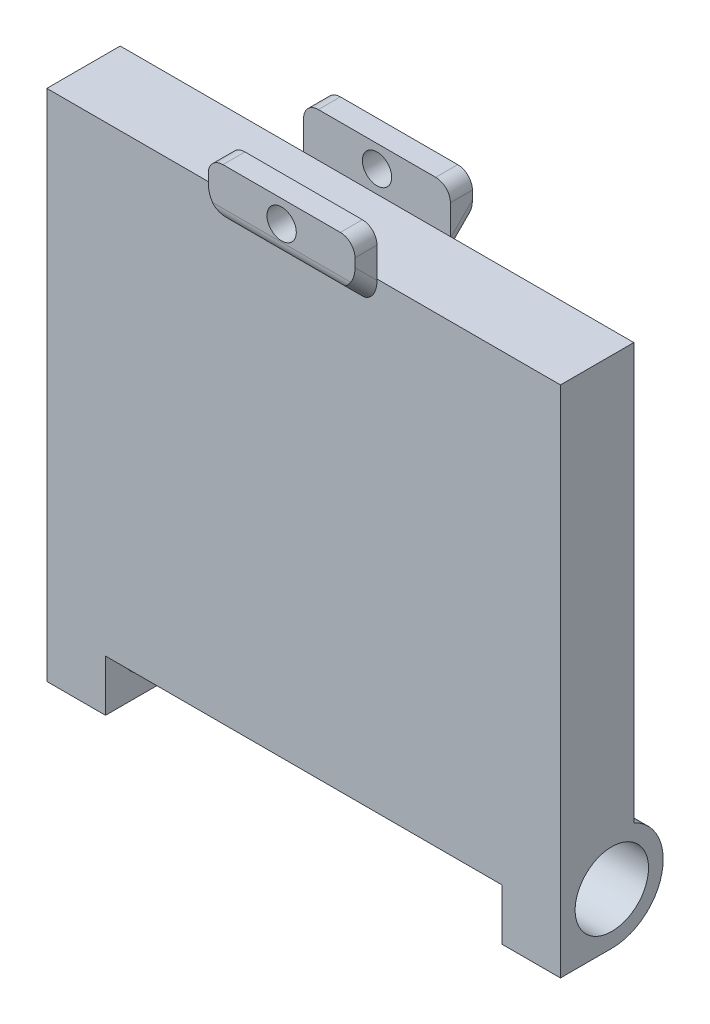
SolidWorks part; units mm, degrees
ref_plane "Front Plane" through (0, 0, 0) normal (0, 0, 1) x (1, 0, 0)
ref_plane "Top Plane" through (0, 0, 0) normal (0, 1, 0) x (1, 0, 0)
ref_plane "Right Plane" through (0, 0, 0) normal (1, 0, 0) x (0, 0, -1)
sketch "Sketch1" plane through (0, 0, 0) normal (0, 0, 1) x (1, 0, 0)
  line L0 (0, 0) -> (0, 31.5)
  line L1 (0, 31.5) -> (35, 31.5)
  line L2 (35, 31.5) -> (35, 0)
  line L3 (35, 0) -> (0, 0)
  dimension "D1" = 31.5
  dimension "D2" = 35
extrude "Boss-Extrude1" add sketch "Sketch1" along normal mid plane 5
sketch "Sketch3" plane through (35, 0, 0) normal (1, 0, 0) x (0, 0, -1)
  line L0 (-2.5, 5.8058) -> (-2.5, 2.251) construction
  line L2 (-2.5, 0) -> (-2.5, 31.5) construction
  line L3 (-2.5, 0) -> (2.5, 0) construction
  circle A0 centre (1, 0) radius 3.5
  point P5 (0, 0)
  dimension "D1" = 7
extrude "Cut-Extrude1" cut sketch "Sketch3" against normal up to surface (35 mm away) up to face at (0, 15.75, 0)
sketch "Sketch4" plane through (35, 0, 0) normal (1, 0, 0) x (0, 0, -1)
  line L0 (-2.5, 0) -> (-2.5, -3.5)
  line L1 (-2.5, -3.5) -> (1, -3.5)
  circle A0 centre (1, 0) radius 3.5
  arc A1 (2.5, 3.1623) -> (-2.5, 0) centre (1, 0) ccw construction
  circle A2 centre (1, 0) radius 2.5
  arc M4 (-2.5, 0) -> (2.5, 3.1623) centre (1, 0) cw
  dimension "D1" = 5
extrude "Boss-Extrude3" add sketch "Sketch4" against normal blind 4 contours A0 A2 M4 | A0 L0 L1 region at (35, -2.7182, 1.7182) region at (35, 2.8744, 0.8179)
ref_plane "Plane2" through (17.5, 0, 0) normal (1, 0, 0) x (0, 0, -1)
mirror "Mirror2" about plane through (17.5, 0, 0) normal (1, 0, 0) of "Boss-Extrude3"
sketch "Sketch5" plane through (17.5, 0, 0) normal (1, 0, 0) x (0, 0, -1)
  line L0 (2.5, 31.5) -> (4, 31.5)
  line L1 (-2.5, 31.5) -> (-4, 31.5)
  line L2 (-4, 31.5) -> (-2.5, 30)
  line L3 (-2.5, -3.5) -> (-2.5, 31.5) construction
  line L4 (4, 31.5) -> (2.5, 30)
  line L5 (2.5, 3.1623) -> (2.5, 31.5) construction
  line L6 (-4, 31.5) -> (-4, 34.5)
  line L7 (-4, 34.5) -> (-2.5, 34.5)
  line L8 (-2.5, 34.5) -> (-2.5, 31.5)
  line L9 (2.5, 31.5) -> (2.5, 34.5)
  line L10 (2.5, 34.5) -> (4, 34.5)
  line L11 (4, 34.5) -> (4, 31.5)
  line L12 (-2.5, 30) -> (-2.5, 31.5)
  line L13 (2.5, 30) -> (2.5, 31.5)
  dimension "D1" = 1.5
  dimension "D2" = 3
extrude "Boss-Extrude4" add sketch "Sketch5" along normal mid plane 10 contours L8 L7 L6 L1 | L2 L12 L1 | L13 L4 L0 | L11 L10 L9 L0 region at (17.5, 33, -3.25) region at (17.5, 31, -3) region at (17.5, 31, 3) region at (17.5, 33, 3.25)
sketch "Sketch6" plane through (0, 0, 4) normal (0, 0, 1) x (1, 0, 0)
  line L0 (17.5, 34.5) -> (17.5, 31.5) construction
  line L1 (22.5, 34.5) -> (12.5, 34.5) construction
  line L2 (22.5, 31.5) -> (12.5, 31.5) construction
  circle A0 centre (17.5, 33) radius 1
  point P8 (17.5, 33)
  dimension "D1" = 2
extrude "Cut-Extrude2" cut sketch "Sketch6" against normal up to surface (8 mm away) up to face at (17.5, 33, -4)
fillet "Fillet1" radius 1 6 edges at (12.5, 30.75, -3.25) (22.5, 30.75, -3.25) (17.5, 31.5, -4) (17.5, 31.5, 4) (12.5, 30.75, 3.25) (22.5, 30.75, 3.25)
fillet "Fillet2" radius 1 4 edges at (12.5, 34.5, -3.25) (12.5, 34.5, 3.25) (22.5, 34.5, -3.25) (22.5, 34.5, 3.25)
